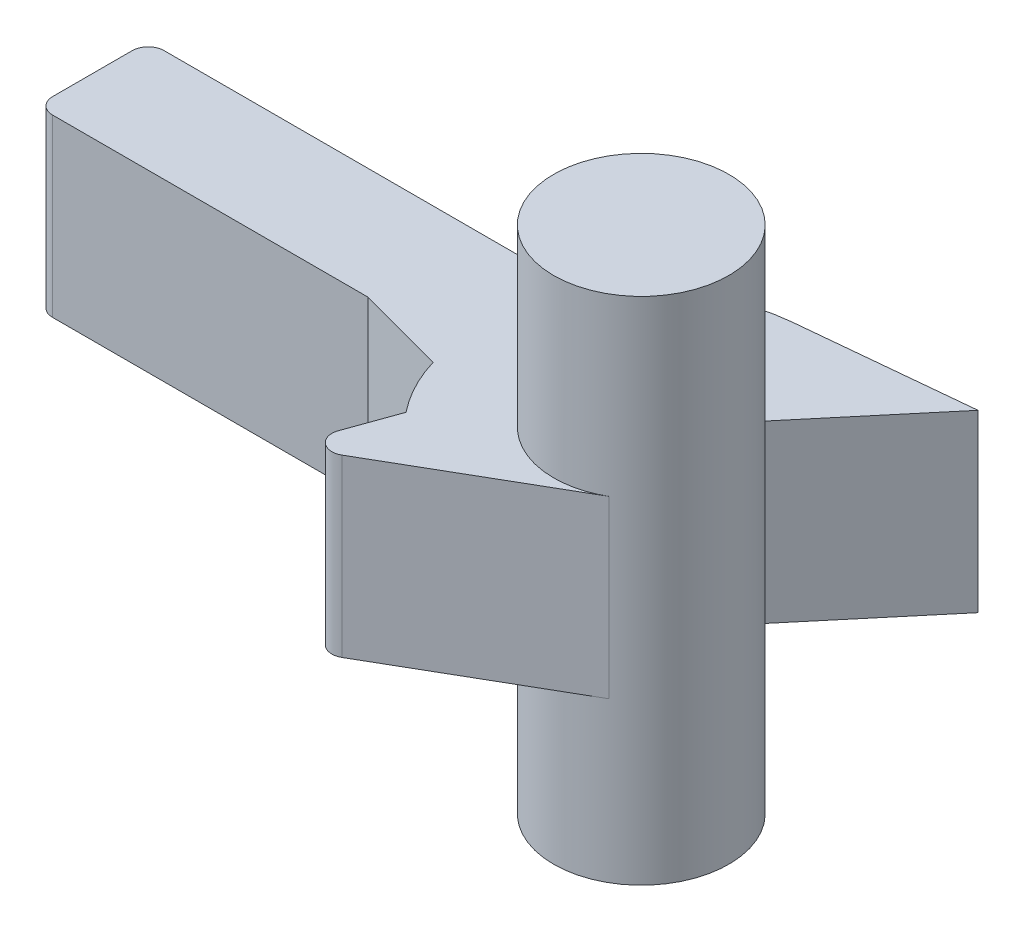
SolidWorks part; units mm, degrees
ref_plane "Front Plane" through (0, 0, 0) normal (0, 0, 1) x (1, 0, 0)
ref_plane "Top Plane" through (0, 0, 0) normal (0, 1, 0) x (1, 0, 0)
ref_plane "Right Plane" through (0, 0, 0) normal (1, 0, 0) x (0, 0, -1)
sketch "Sketch1" plane through (0, 0, 0) normal (0, 1, 0) x (1, 0, 0)
  line L8 (0.7778, -0.7778) -> (-0.7778, 0.7778) construction
  line L9 (-7.2889, 1.1) -> (-1.7889, 1.1)
  line L10 (0, 0) -> (-1.1, 0) construction
  line L11 (-7.2889, 1.1) -> (-7.2889, -0.3)
  line L12 (-7.2889, -0.3) -> (-3.1305, -0.3)
  line L13 (-3.1305, -0.3) -> (-0.2847, -1.0625) construction
  line L14 (-0.2847, -1.0625) -> (0, 0) construction
  line L15 (0, 0) -> (-0.2039, 2.0901) construction
  line L17 (1.9284, 2.2981) -> (-0.2039, 2.0901)
  line L18 (0, 0) -> (0.55, -0.9526) construction
  line L19 (0, 1.1) -> (-7.2889, 1.1) construction
  line L20 (-2.0126, -0.5995) -> (-3.1305, -0.3)
  line L22 (0.55, -0.9526) -> (-2.0481, -2.4526)
  line L24 (-2.0481, -2.4526) -> (-1.6393, -1.3126)
  line L26 (0, 0) -> (1.9284, 2.2981)
  circle A0 centre (0, 0) radius 1.1
  circle A1 centre (0, 0) radius 2.1 construction
  arc A2 (-1.7889, 1.1) -> (-0.2039, 2.0901) centre (0, 0) cw
  arc A7 (-1.6393, -1.3126) -> (-2.0126, -0.5995) centre (0, 0) cw
  point P10 (0, 0)
  dimension "D1" = 2.2
  dimension "D2" = 45
  dimension "D5" = 1
  dimension "D6" = 60
  dimension "D3" = 85
  dimension "D4" = 3
  dimension "D8" = 15
  dimension "D9" = 1.4
  dimension "D10" = 5.5
  dimension "D13" = 3
extrude "Boss-Extrude1" add sketch "Sketch1" along normal blind 2.2 contours A0 | A0 region at (-2.7705, 0, -0.3918) region at (0.9687, 0, -0.4517)
extrude "Boss-Extrude2" add sketch "Sketch1<3>" along normal blind 4.4 and the other way blind 2 contours A0 region at (0.9687, 0, -0.4517)
sketch "Sketch1<3>" plane through (0, 0, 0) normal (0, 1, 0) x (1, 0, 0) same geometry as "Sketch1"
fillet "Fillet1" radius 0.2 3 edges at (-2.0481, 1.1, 2.4526) (-7.2889, 1.1, 0.3) (-7.2889, 1.1, -1.1)
